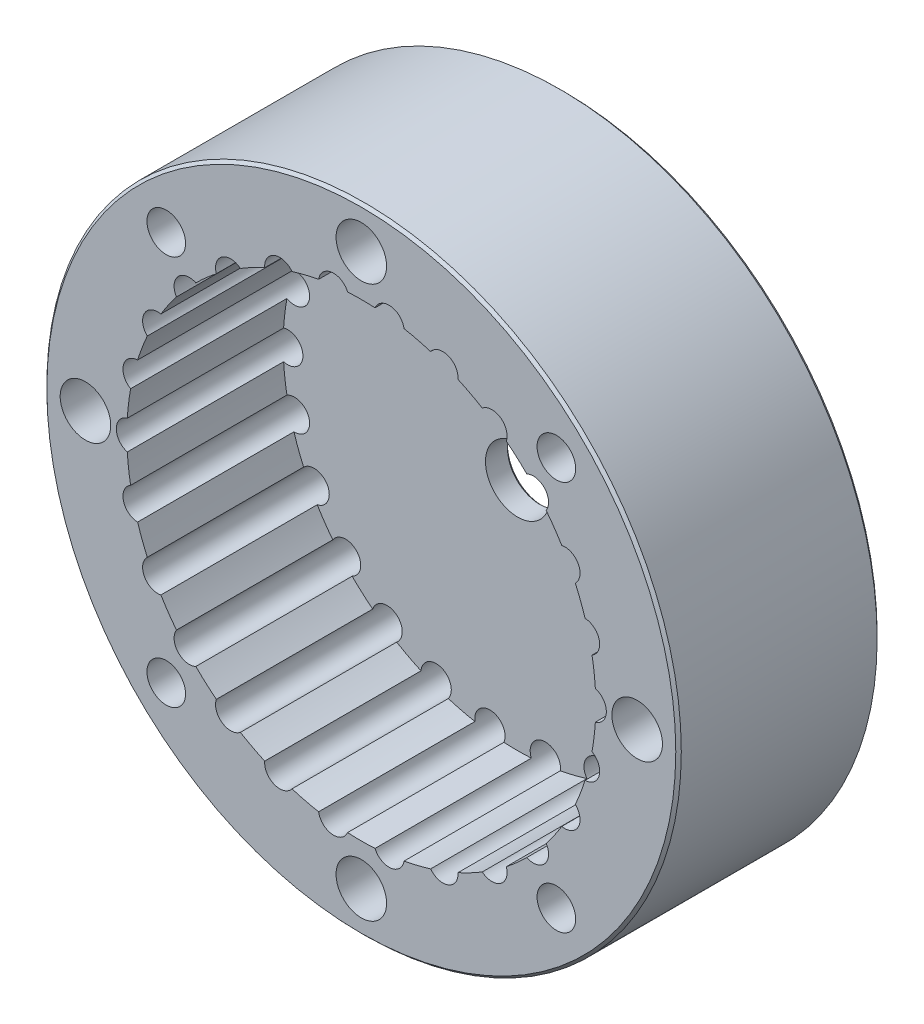
SolidWorks part; units mm, degrees
ref_plane "Front Plane" through (0, 0, 0) normal (0, 0, 1) x (1, 0, 0)
ref_plane "Top Plane" through (0, 0, 0) normal (0, 1, 0) x (1, 0, 0)
ref_plane "Right Plane" through (0, 0, 0) normal (1, 0, 0) x (0, 0, -1)
sketch "Sketch1" plane through (0, 0, 0) normal (0, 0, 1) x (1, 0, 0)
  line L0 (-25, 0) -> (25, 0) construction
  circle A0 centre (0, 0) radius 34.5
  circle A1 centre (0, 0) radius 25.5
  circle A2 centre (25, 0) radius 1.65
  circle A3 centre (24.2735, -5.9829) radius 1.65
  circle A4 centre (22.1364, -11.6181) radius 1.65
  circle A5 centre (18.7128, -16.5781) radius 1.65
  circle A6 centre (14.2016, -20.5746) radius 1.65
  circle A7 centre (8.8651, -23.3754) radius 1.65
  circle A8 centre (3.0134, -24.8177) radius 1.65
  circle A9 centre (-3.0134, -24.8177) radius 1.65
  circle A10 centre (-8.8651, -23.3754) radius 1.65
  circle A11 centre (-14.2016, -20.5746) radius 1.65
  circle A12 centre (-18.7128, -16.5781) radius 1.65
  circle A13 centre (-22.1364, -11.6181) radius 1.65
  circle A14 centre (-24.2735, -5.9829) radius 1.65
  circle A15 centre (-25, 0) radius 1.65
  circle A16 centre (-24.2735, 5.9829) radius 1.65
  circle A17 centre (-22.1364, 11.6181) radius 1.65
  circle A18 centre (-18.7128, 16.5781) radius 1.65
  circle A19 centre (-14.2016, 20.5746) radius 1.65
  circle A20 centre (-8.8651, 23.3754) radius 1.65
  circle A21 centre (-3.0134, 24.8177) radius 1.65
  circle A22 centre (3.0134, 24.8177) radius 1.65
  circle A23 centre (8.8651, 23.3754) radius 1.65
  circle A24 centre (14.2016, 20.5746) radius 1.65
  circle A25 centre (18.7128, 16.5781) radius 1.65
  circle A26 centre (22.1364, 11.6181) radius 1.65
  circle A27 centre (24.2735, 5.9829) radius 1.65
  point P7 (0, 0)
  point P61 (0, 0)
  dimension "D1" = 69
  dimension "D2" = 51
  dimension "D4" = 3.3
  dimension "D3" = 50
  dimension "D5" = 26
extrude "Boss-Extrude2" add sketch "Sketch1" along normal blind 17 contours A0 A27 A1 A2 A3 A4 A5 A6 A7 A8 A9 A10 A11 A12 A13 A14 A15 A16 A17 A18 A19 A20 A21 A22 A23 A24 A25 | A1 A17 | A1 A18 | A1 A19 | A1 A20 | A1 A21 | A1 A22 | A1 A23 | A1 A24 | A1 A25 | A1 A26 | A1 A27 | A1 A2 | A1 A4 | A1 A5 | A1 A6 | A1 A7 | A1 A8 | A1 A9 | A1 A10 | A1 A11 | A1 A12 | A1 A13 | A1 A14 | A1 A15 | A1 A16 | A1 A3 region at (-33.5242, 0, 0) region at (25.9679, 0, 0) region at (25.2133, 6.2145, 0) region at (25.2133, -6.2145, 0) region at (22.9934, 12.0679, 0) region at (22.9934, -12.0679, 0) region at (19.4373, 17.2199, 0) region at (19.4373, -17.2199, 0) region at (14.7514, 21.3712, 0) region at (14.7514, -21.3712, 0) region at (9.2083, 24.2804, 0) region at (9.2083, -24.2804, 0) region at (3.1301, 25.7786, 0) region at (3.1301, -25.7786, 0) region at (-3.1301, 25.7786, 0) region at (-3.1301, -25.7786, 0) region at (-9.2083, 24.2804, 0) region at (-9.2083, -24.2804, 0) region at (-14.7514, 21.3712, 0) region at (-14.7514, -21.3712, 0) region at (-19.4373, 17.2199, 0) region at (-19.4373, -17.2199, 0) region at (-22.9934, 12.0679, 0) region at (-22.9934, -12.0679, 0) region at (-25.2133, 6.2145, 0) region at (-25.2133, -6.2145, 0) region at (-25.9679, 0, 0)
extrude "Boss-Extrude3" add sketch "Sketch1<3>" against normal blind 5 contours A15 L0 A2 A1 A27 A26 A25 A24 A23 A22 A21 A20 A19 A18 A17 A16 | L0 A15 A1 A14 A13 A12 A11 A10 A9 A8 A7 A6 A5 A4 A3 A2 | A0 A27 A1 A2 A3 A4 A5 A6 A7 A8 A9 A10 A11 A12 A13 A14 A15 A16 A17 A18 A19 A20 A21 A22 A23 A24 A25 | A9 | A10 | A11 | A12 | A13 | A14 | A15 | A16 | A17 | A18 | A19 | A20 | A21 | A22 | A23 | A24 | A25 | A26 | A27 | A2 | A3 | A4 | A5 | A6 | A7 | A8 region at (0, 10.4374, 0) region at (0, -10.4374, 0) region at (-33.5242, 0, 0)
sketch "Sketch1<3>" plane through (0, 0, 0) normal (0, 0, 1) x (1, 0, 0) same geometry as "Sketch1"
extrude "Cut-Extrude4" cut sketch "Sketch1<5>" against normal blind 3 and the other way through all contours A18 | A19 | A20 | A21 | A22 | A23 | A24 | A25 | A26 | A27 | A2 | A3 | A4 | A5 | A6 | A7 | A8 | A9 | A10 | A11 | A12 | A13 | A14 | A15 | A16 | A17
sketch "Sketch1<5>" plane through (0, 0, 0) normal (0, 0, 1) x (1, 0, 0) same geometry as "Sketch1"
sketch "Sketch3" plane through (0, 0, 0) normal (0, 0, 1) x (1, 0, 0)
  line L0 (0, 30) -> (0, 0) construction
  circle A0 centre (0, 30) radius 1.8
  circle A1 centre (30, 0) radius 1.8
  circle A2 centre (0, -30) radius 1.8
  circle A3 centre (-30, 0) radius 1.8
  circle A8 centre (0, 0) radius 3.5
  circle A9 centre (0, 0) radius 30 construction
  point P0 (0, 0)
  point P21 (0, 0)
  dimension "D3" = 4
  dimension "D4" = 7
  dimension "D1" = 60
  dimension "D2" = 3.6
extrude "Cut-Extrude6" cut sketch "Sketch3" against normal through all both and the other way through all
sketch "Sketch4" plane through (0, 0, -5) normal (0, 0, -1) x (-1, 0, 0)
  circle A0 centre (0, 0) radius 10.15
  dimension "D1" = 20.3
extrude "Cut-Extrude7" cut sketch "Sketch4" against normal blind 2.3
sketch "Sketch6" plane through (0, 0, 17) normal (0, 0, 1) x (1, 0, 0)
  line L0 (0, 0) -> (0, 30) construction
  line L1 (-21.2132, 21.2132) -> (0, 0) construction
  circle A0 centre (-21.2132, 21.2132) radius 2.1
  circle A1 centre (21.2132, 21.2132) radius 2.1
  circle A2 centre (21.2132, -21.2132) radius 2.1
  circle A3 centre (-21.2132, -21.2132) radius 2.1
  point P15 (0, 0)
  dimension "D1" = 4.2
  dimension "D2" = 30
  dimension "D3" = 45
  dimension "D4" = 4
extrude "Cut-Extrude8" cut sketch "Sketch6" against normal blind 10 contours A0 | A1 | A3 | A2 region at (-21.2132, 21.2132, 17) region at (21.2132, 21.2132, 17) region at (21.2132, -21.2132, 17) region at (-21.2132, -21.2132, 17)
sketch "Sketch7" plane through (0, 0, 17) normal (0, 0, 1) x (1, 0, 0)
  circle A0 centre (0, 30) radius 2.75
  circle A1 centre (30, 0) radius 2.75
  circle A2 centre (0, -30) radius 2.75
  circle A3 centre (-30, 0) radius 2.75
  circle A4 centre (0, 0) radius 30 construction
  point P12 (0, 0)
  dimension "D1" = 5.5
  dimension "D3" = 60
  dimension "D2" = 4
extrude "Cut-Extrude9" cut sketch "Sketch7" against normal blind 10
chamfer "Chamfer1" distance 0.4 angle 45 5 edges at (-10.15, 0, -5) (1.8, -30, -5) (-28.2, 0, -5) (31.8, 0, -5) (1.8, 30, -5)
chamfer "Chamfer2" distance 0.3 angle 45 1 edges at (-3.5, 0, -2.7)
chamfer "Chamfer3" distance 0.4 angle 45 1 edges at (34.5, 0, -5)
chamfer "Chamfer4" distance 0.3 angle 45 1 edges at (34.5, 0, 17)
equation "\"N_pins\"= 26"
equation "\"N_lobes\"= \"N_pins\" - 1"
equation "\"R_pc\"= 25"
equation "\"D_pin\"= 3.3"
equation "\"R_pin\"= \"D_pin\" / 2"
equation "\"ecc\"= 0.72"
equation "\"t_disc\"= 7"
equation "\"N_out\"= 8"
equation "\"D_outc\"=22"
equation "\"D_roller\"= 5"
equation "\"D_outhole\"= \"D_roller\" + 2 * \"ecc\""
equation "\"D_cam_OD\"= 21"
equation "\"D_cam_ID\"= 10"
equation "\"clr_bore\"= 1"
equation "\"D_bore\"= 2 * \"R_pc\" + \"clr_bore\""
equation "\"t_wall\"= 7.5"
equation "\"D_housing\"= 69"
equation "\"D1@Sketch1\"=\"D_housing\""
equation "\"D2@Sketch1\"=\"D_bore\""
equation "\"D3@Sketch1\"=2 * \"R_pc\""
equation "\"D4@Sketch1\"=\"D_pin\""
equation "\"L_housing\"=17"
equation "\"D1@Boss-Extrude2\"=\"L_housing\""
